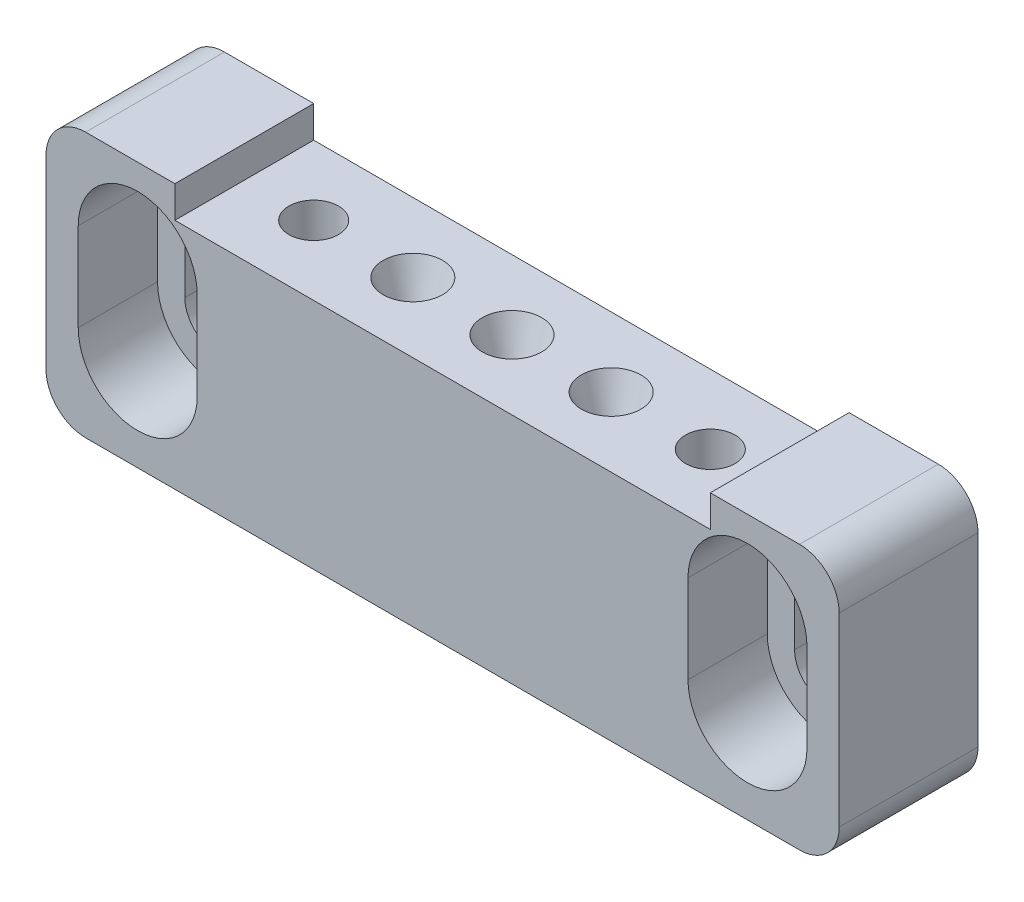
SolidWorks part; units mm, degrees
ref_plane "Front Plane" through (0, 0, 0) normal (0, 0, 1) x (1, 0, 0)
ref_plane "Top Plane" through (0, 0, 0) normal (0, 1, 0) x (1, 0, 0)
ref_plane "Right Plane" through (0, 0, 0) normal (1, 0, 0) x (0, 0, -1)
sketch "Sketch1" plane through (0, 0, 0) normal (0, 0, 1) x (1, 0, 0)
  line L0 (0, 0) -> (18, 0)
  line L1 (20, 2) -> (20, 11.9458)
  line L2 (19.1303, 13.5958) -> (10.5109, 19.5)
  line L3 (9.3807, 19.85) -> (-9.3807, 19.85)
  line L4 (-10.5109, 19.5) -> (-19.1303, 13.5958)
  line L5 (-20, 11.9458) -> (-20, 2)
  line L6 (-18, 0) -> (0, 0)
  line L7 (0, 19.85) -> (0, 0) construction
  line L8 (-15.375, 9.075) -> (-15.375, 4.625) construction
  line L9 (-13.75, 9.075) -> (-13.75, 4.625)
  line L10 (-17, 9.075) -> (-17, 4.625)
  line L11 (15.375, 9.075) -> (15.375, 4.625) construction
  line L12 (17, 9.075) -> (17, 4.625)
  line L13 (13.75, 9.075) -> (13.75, 4.625)
  arc A0 (-13.75, 9.075) -> (-17, 9.075) centre (-15.375, 9.075) ccw
  arc A1 (-17, 4.625) -> (-13.75, 4.625) centre (-15.375, 4.625) ccw
  arc A2 (17, 9.075) -> (13.75, 9.075) centre (15.375, 9.075) ccw
  arc A3 (13.75, 4.625) -> (17, 4.625) centre (15.375, 4.625) ccw
  arc A4 (-9.3807, 19.85) -> (-10.5109, 19.5) centre (-9.3807, 17.85) ccw
  arc A5 (9.3807, 19.85) -> (10.5109, 19.5) centre (9.3807, 17.85) cw
  arc A6 (-20, 11.9458) -> (-19.1303, 13.5958) centre (-18, 11.9458) cw
  arc A7 (19.1303, 13.5958) -> (20, 11.9458) centre (18, 11.9458) cw
  arc A8 (20, 2) -> (18, 0) centre (18, 2) cw
  arc A9 (-20, 2) -> (-18, 0) centre (-18, 2) ccw
  point P10 (-15.375, 6.85)
  point P16 (15.375, 6.85)
  point P23 (15.375, 3)
  point P24 (-15.375, 3)
  point P25 (-15.375, 10.7)
  point P28 (-10, 19.85)
  point P31 (10, 19.85)
  point P34 (-20, 13)
  point P37 (20, 13)
  point P40 (20, 0)
  point P43 (-20, 0)
  dimension "D14" = 2
  dimension "D1" = 20
  dimension "D2" = 20
  dimension "D3" = 19.85
  dimension "D4" = 13
  dimension "D5" = 13
  dimension "D6" = 20
  dimension "D7" = 3.25
  dimension "D8" = 3.25
  dimension "D9" = 3
  dimension "D10" = 3
  dimension "D11" = 7.7
  dimension "D12" = 3
  dimension "D13" = 3
extrude "Boss-Extrude1" add sketch "Sketch1" along normal blind 7
sketch "Sketch2" plane through (0, 0, 7) normal (0, 0, 1) x (1, 0, 0)
  line L0 (-15.375, 4.625) -> (-15.375, 9.075) construction
  line L1 (-18.375, 4.625) -> (-18.375, 9.075)
  line L2 (-12.375, 4.625) -> (-12.375, 9.075)
  line L3 (15.375, 4.625) -> (15.375, 9.075) construction
  line L4 (12.375, 4.625) -> (12.375, 9.075)
  line L5 (18.375, 4.625) -> (18.375, 9.075)
  arc A0 (-18.375, 4.625) -> (-12.375, 4.625) centre (-15.375, 4.625) ccw
  arc A1 (-12.375, 9.075) -> (-18.375, 9.075) centre (-15.375, 9.075) ccw
  arc A2 (12.375, 4.625) -> (18.375, 4.625) centre (15.375, 4.625) ccw
  arc A3 (18.375, 9.075) -> (12.375, 9.075) centre (15.375, 9.075) ccw
  point P4 (-15.375, 6.85)
  point P9 (15.375, 6.85)
  dimension "D1" = 6
  dimension "D2" = 6
extrude "ScrewHeadClearance" cut sketch "Sketch2" against normal blind 4
sketch "Sketch6" plane through (0, 0, 7) normal (0, 0, 1) x (1, 0, 0)
  line L0 (-20, 11.9458) -> (-20, 2) construction
  line L1 (-13.5, 13.35) -> (-6.5, 13.35)
  line L2 (-13.5, 13.35) -> (-13.5, 11.75)
  line L3 (-13.5, 11.75) -> (13.5, 11.75)
  line L4 (13.5, 13.35) -> (13.5, 11.75)
  line L5 (-13.5, 13.35) -> (13.5, 11.75) construction
  line L6 (-13.5, 11.75) -> (13.5, 13.35) construction
  line L7 (20, 2) -> (20, 11.9458) construction
  line L8 (-18, 0) -> (18, 0) construction
  line L9 (-6.5, 13.35) -> (-6.5, 19.85)
  line L11 (-6.5, 19.85) -> (6.5, 19.85)
  line L12 (6.5, 19.85) -> (6.5, 13.35)
  line L14 (6.5, 13.35) -> (13.5, 13.35)
  line L15 (9.3807, 19.85) -> (-9.3807, 19.85) construction
  point P4 (0, 12.55)
  dimension "D1" = 6.5
  dimension "D2" = 6.5
  dimension "D3" = 11.75
  dimension "D4" = 1.6
  dimension "D5" = 7
  dimension "D6" = 7
  dimension "D7" = 13
  dimension "D8" = 6.5
  dimension "D9" = 0
extrude "PCB Cutout" cut sketch "Sketch6" against normal through all
sketch "Sketch8" plane through (0, 19.85, 0) normal (0, 1, 0) x (1, 0, 0)
  line L0 (-6.5, 0) -> (-9.3807, 0) construction
  line L1 (9.3807, 0) -> (6.5, 0) construction
  circle A0 centre (-10, -3.5) radius 1.25
  circle A1 centre (10, -3.5) radius 1.25
  dimension "D1" = 2.5
  dimension "D2" = 10
  dimension "D4" = 3.5
  dimension "D5" = 3.5
  dimension "D3" = 10
extrude "ScrewThreads" cut sketch "Sketch8" against normal blind 16
sketch "Sketch9" plane through (0, 19.85, 0) normal (0, 1, 0) x (1, 0, 0)
  circle A0 centre (10, -3.5) radius 3
  circle A1 centre (-10, -3.5) radius 3
  dimension "D1" = 6
extrude "Cut-Extrude6" cut sketch "Sketch9" against normal up to surface (8.1 mm away) up to face at (-10, 11.75, 2.25)
sketch "Sketch10" plane through (0, 0, 7) normal (0, 0, 1) x (1, 0, 0)
  line L0 (-6.5, 13.35) -> (-13.5, 13.35) construction
  line L1 (-20, 19.85) -> (20, 19.85)
  line L2 (-20, 19.85) -> (-20, 13.35)
  line L3 (-20, 13.35) -> (20, 13.35)
  line L4 (20, 19.85) -> (20, 13.35)
  line L5 (-20, 19.85) -> (20, 13.35) construction
  line L6 (-20, 13.35) -> (20, 19.85) construction
  line L7 (-20, 11.9458) -> (-20, 2) construction
  line L8 (20, 2) -> (20, 11.9458) construction
  line L9 (9.3807, 19.85) -> (6.5, 19.85) construction
  point P4 (0, 16.6)
extrude "Cut-Extrude7" cut sketch "Sketch10" against normal through all
fillet "Fillet1" radius 2 2 edges at (-19.4241, 13.35, 3.5) (19.4241, 13.35, 3.5)
sketch "Sketch11" plane through (0, 11.75, 0) normal (0, 1, 0) x (1, 0, 0)
  line L0 (-10, -3.5) -> (10, -3.5) construction
  line L1 (0, 0) -> (0, -6.3575) construction
  circle A0 centre (0, -3.5) radius 1.5
  circle A1 centre (5, -3.5) radius 1.5
  circle A2 centre (-5, -3.5) radius 1.5
  dimension "D1" = 3
  dimension "D2" = 5
  dimension "D3" = 5
extrude "ClearanceHoles" cut sketch "Sketch11" against normal blind 3 draft 20
